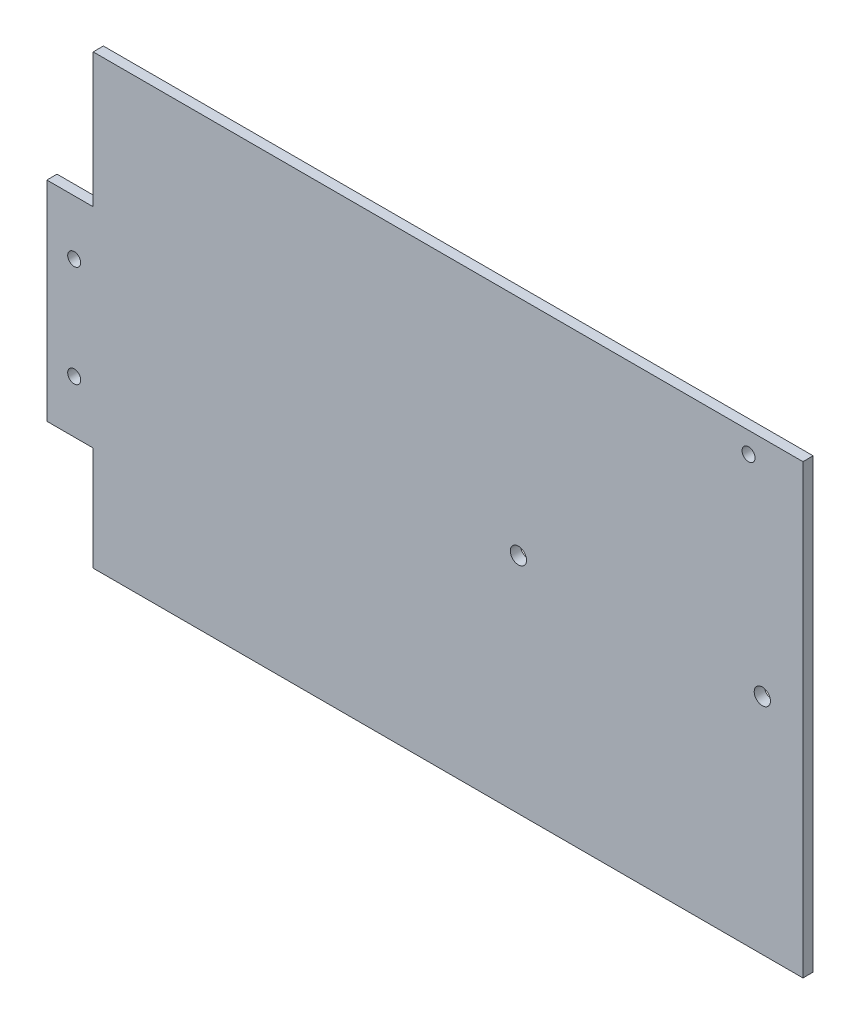
SolidWorks part; units mm, degrees
ref_plane "Front Plane" through (0, 0, 0) normal (0, 0, 1) x (1, 0, 0)
ref_plane "Top Plane" through (0, 0, 0) normal (0, 1, 0) x (1, 0, 0)
ref_plane "Right Plane" through (0, 0, 0) normal (1, 0, 0) x (0, 0, -1)
sketch "Sketch1" plane through (0, 0, 0) normal (0, 0, 1) x (1, 0, 0)
  line L0 (-221.742, 69.85) -> (0, 69.85) construction
  line L1 (0, 0) -> (-221.742, 0)
  line L2 (0, 0) -> (0, 139.7)
  line L3 (0, 139.7) -> (-221.742, 139.7)
  line L4 (-221.742, 0) -> (-221.742, 139.7)
  line L5 (-110.871, 139.7) -> (-110.871, 0) construction
  line L6 (-221.742, 97.79) -> (-236.22, 97.79)
  line L7 (-221.742, 32.512) -> (-236.22, 32.512)
  line L8 (-236.22, 97.79) -> (-236.22, 32.512)
  line L9 (-303.3951, 65.151) -> (-302.9884, 65.151)
  dimension "D1" = 139.7
  dimension "D2" = 221.742
  dimension "D3" = 41.91
  dimension "D4" = 32.512
  dimension "D5" = 14.478
extrude "Boss-Extrude3" add sketch "Sketch1" along normal blind 3.175 contours L4 L1 L2 L3 | L6 L8 L7 L4 region at (-110.871, 69.85, 0) region at (-228.981, 65.151, 0)
sketch "Sketch3" plane through (0, 0, 0) normal (0, 0, -1) x (-1, 0, 0)
  circle A0 centre (227.6801, 80.6813) radius 2.032
  circle A1 centre (227.6801, 48.9313) radius 2.032
  dimension "D1" = 4.064
  dimension "D2" = 4.064
extrude "Cut-Extrude2" cut sketch "Sketch3" against normal through all
sketch "Sketch4" plane through (0, 0, 3.175) normal (0, 0, 1) x (1, 0, 0)
  line L0 (0, 0) -> (0, 139.7) construction
  line L1 (0, 139.7) -> (-221.742, 139.7) construction
  circle A0 centre (-17, 133.2) radius 2.032
  dimension "D1" = 4.064
  dimension "D2" = 17
  dimension "D3" = 6.5
extrude "Cut-Extrude3" cut sketch "Sketch4" against normal through all
sketch "Sketch5" plane through (0, 0, 3.175) normal (0, 0, 1) x (1, 0, 0)
  line L0 (0, 0) -> (0, 139.7) construction
  line L1 (0, 0) -> (-221.742, 0) construction
  circle A0 centre (-88.9, 69.85) radius 2.54
  circle A1 centre (-12.7, 69.85) radius 2.54
  dimension "D2" = 5.08
  dimension "D3" = 5.08
  dimension "D1" = 76.2
  dimension "D4" = 12.7
  dimension "D5" = 69.85
extrude "Cut-Extrude4" cut sketch "Sketch5" against normal through all
